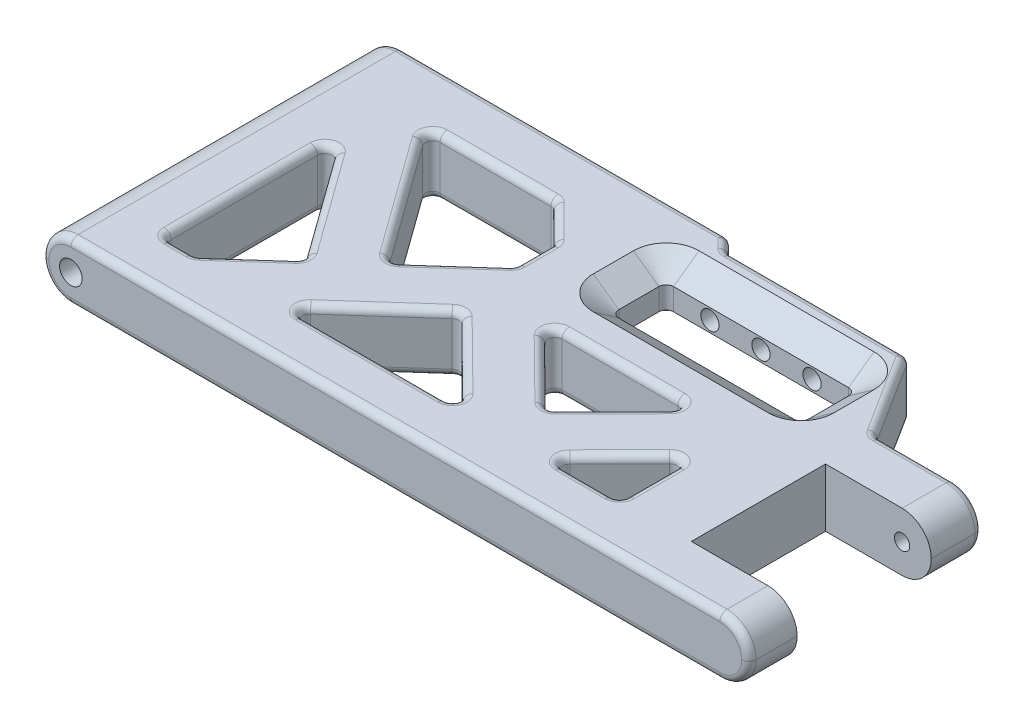
SolidWorks part; units mm, degrees
ref_plane "Plan de face" through (0, 0, 0) normal (0, 0, 1) x (1, 0, 0)
ref_plane "Plan de dessus" through (0, 0, 0) normal (0, 1, 0) x (1, 0, 0)
ref_plane "Plan de droite" through (0, 0, 0) normal (1, 0, 0) x (0, 0, -1)
sketch "Esquisse1" plane through (0, 0, 0) normal (0, 1, 0) x (1, 0, 0)
  line L0 (97, 2.25) -> (97, 9.25)
  line L19 (0, 22.75) -> (48.2586, 22.75)
  line L20 (0, 22.75) -> (0, -22.75)
  line L21 (32.0858, 15) -> (16.8865, 15)
  line L22 (16.0755, 13.415) -> (27.68, -2.6721)
  line L23 (37.2071, 10.2929) -> (32.7929, 14.7071)
  line L24 (37.5, 5.0644) -> (37.5, 9.5858)
  line L25 (29.1571, -2.833) -> (37.166, 4.3185)
  line L26 (21.8025, -8.1987) -> (11.811, 5.6522)
  line L27 (10, 5.0672) -> (10, -15)
  line L28 (14.6959, -15.7459) -> (21.6575, -9.5296)
  line L29 (38.632, -5.0977) -> (28.3777, -14.2541)
  line L30 (49.2684, -14.2886) -> (40.0009, -5.1322)
  line L31 (47.9211, -1.7114) -> (55.9463, -9.6404)
  line L32 (11, -16) -> (14.0298, -16)
  line L33 (29.0437, -16) -> (48.5656, -16)
  line L35 (97, -22.75) -> (0, -22.75)
  line L64 (48.9737, 22.449) -> (50.1934, 21.201)
  line L65 (50.9086, 20.9) -> (74.5358, 20.9)
  line L67 (48.5, 15.4) -> (72.5, 15.4)
  line L69 (47.5, 8.9) -> (47.5, 14.4)
  line L72 (72.5, 7.9) -> (48.5, 7.9)
  line L75 (73.5, 14.4) -> (73.5, 8.9)
  line L78 (75.3812, 20.4342) -> (82.1547, 9.7158)
  line L79 (83, 9.25) -> (97, 9.25)
  line L80 (97, -22.75) -> (97, -16.15)
  line L82 (82.5, 2.25) -> (82.5, -16.15)
  line L83 (97, 2.25) -> (82.5, 2.25)
  line L86 (82.5, -16.15) -> (97, -16.15)
  line L87 (64.4832, 0) -> (48.6239, 0)
  line L88 (57.3605, -9.6319) -> (65.1945, -1.7028)
  line L89 (64.7086, -16) -> (71.5, -16)
  line L90 (72.5, -15) -> (72.5, -8.1262)
  line L91 (70.7886, -7.4234) -> (63.9973, -14.2972)
  arc A16 (16.8865, 15) -> (16.0755, 13.415) centre (16.8865, 14) ccw
  arc A17 (32.7929, 14.7071) -> (32.0858, 15) centre (32.0858, 14) ccw
  arc A18 (37.5, 9.5858) -> (37.2071, 10.2929) centre (36.5, 9.5858) ccw
  arc A19 (37.166, 4.3185) -> (37.5, 5.0644) centre (36.5, 5.0644) ccw
  arc A20 (27.68, -2.6721) -> (29.1571, -2.833) centre (28.491, -2.0871) ccw
  arc A21 (21.6575, -9.5296) -> (21.8025, -8.1987) centre (20.9914, -8.7837) ccw
  arc A22 (11.811, 5.6522) -> (10, 5.0672) centre (11, 5.0672) ccw
  arc A23 (40.0009, -5.1322) -> (38.632, -5.0977) centre (39.298, -5.8436) ccw
  arc A24 (48.6239, 0) -> (47.9211, -1.7114) centre (48.6239, -1) ccw
  arc A25 (10, -15) -> (11, -16) centre (11, -15) ccw
  arc A26 (14.0298, -16) -> (14.6959, -15.7459) centre (14.0298, -15) ccw
  arc A27 (28.3777, -14.2541) -> (29.0437, -16) centre (29.0437, -15) ccw
  arc A28 (48.5656, -16) -> (49.2684, -14.2886) centre (48.5656, -15) ccw
  arc A45 (48.9737, 22.449) -> (48.2586, 22.75) centre (48.2586, 21.75) ccw
  arc A46 (50.1934, 21.201) -> (50.9086, 20.9) centre (50.9086, 21.9) ccw
  arc A47 (48.5, 15.4) -> (47.5, 14.4) centre (48.5, 14.4) ccw
  arc A48 (47.5, 8.9) -> (48.5, 7.9) centre (48.5, 8.9) ccw
  arc A49 (73.5, 14.4) -> (72.5, 15.4) centre (72.5, 14.4) ccw
  arc A50 (72.5, 7.9) -> (73.5, 8.9) centre (72.5, 8.9) ccw
  arc A51 (75.3812, 20.4342) -> (74.5358, 20.9) centre (74.5358, 19.9) ccw
  arc A52 (82.1547, 9.7158) -> (83, 9.25) centre (83, 10.25) ccw
  arc A55 (65.1945, -1.7028) -> (64.4832, 0) centre (64.4832, -1) ccw
  arc A56 (55.9463, -9.6404) -> (57.3605, -9.6319) centre (56.6492, -8.9291) ccw
  arc A57 (63.9973, -14.2972) -> (64.7086, -16) centre (64.7086, -15) ccw
  arc A58 (71.5, -16) -> (72.5, -15) centre (71.5, -15) ccw
  arc A59 (72.5, -8.1262) -> (70.7886, -7.4234) centre (71.5, -8.1262) ccw
  dimension "D4" = 1
  dimension "D1" = 97
  dimension "D2" = 45.5
  dimension "D3" = 32
  dimension "D5" = 26
  dimension "D6" = 7.5
  dimension "D7" = 5.5
  dimension "D8" = 23.5
  dimension "D9" = 43.65
  dimension "D10" = 7
  dimension "D11" = 6.6
  dimension "D12" = 14.5
  dimension "D13" = 2.65
  dimension "D14" = 8.4642
  dimension "D15" = 14
  dimension "D16" = 23.6273
  dimension "D17" = 8
  dimension "D18" = 8
  dimension "D19" = 8
  dimension "D20" = 8
  dimension "D21" = 10
extrude "Boss.-Extru.1" add sketch "Esquisse1" along normal blind 4 and the other way blind 4
fillet "Congé1" radius 4 6 edges at (0, 4, 0) (97, -4, -5.75) (97, -4, 19.45) (97, 4, 19.45) (97, 4, -5.75) (0, -4, 0)
fillet "Congé2" radius 1 100 edges at (71.8799, -4, 7.2012) (72.5, -4, 11.5631) (72.2071, -4, 15.7071) (68.1043, -4, 16) (63.7859, -4, 15.3855) (47.6989, -4, 0.6201) (56.5535, -4, 0) (65.4059, -4, 0.6145) (61.2775, -4, 5.6674) (56.6552, -4, 9.929) (37.4127, -4, -4.6558) (33.1616, -4, -0.7428) (28.3828, -4, 3.0812) (21.8778, -4, -5.3714) (15.9963, -4, -14.4555) (24.4861, -4, -15) (32.4685, -4, -14.9239) (35, -4, -12.5) (37.4239, -4, -9.9685) (39.3233, -4, 4.8439) (44.6346, -4, 9.7104) (49.4906, -4, 15.3799) (38.8047, -4, 16) (28.1094, -4, 15.3564) (14.3863, -4, 15.9343) (12.5149, -4, 16) (10.2929, -4, 15.7071) (10, -4, 4.9664) (10.6926, -4, -6.0187) (16.8067, -4, 1.2733) (21.9856, -4, 8.892) (49.4906, 4, 15.3799) (38.8047, 4, 16) (28.1094, 4, 15.3564) (33.5048, 4, 9.6759) (39.3233, 4, 4.8439) (71.8799, 4, 7.2012) (72.5, 4, 11.5631) (72.2071, 4, 15.7071) (68.1043, 4, 16) (63.7859, 4, 15.3855) (65.4059, 4, 0.6145) (61.2775, 4, 5.6674) (56.6552, 4, 9.929) (51.9337, 4, 5.6759) (47.6989, 4, 0.6201) (15.9963, 4, -14.4555) (24.4861, 4, -15) (32.4685, 4, -14.9239) (35, 4, -12.5) (37.4239, 4, -9.9685) (37.5, 4, -7.3251) (37.4127, 4, -4.6558) (33.1616, 4, -0.7428) (28.3828, 4, 3.0812) (10.6926, 4, -6.0187) (16.8067, 4, 1.2733) (21.9856, 4, 8.892) (18.1767, 4, 12.6378) (14.3863, 4, 15.9343) (12.5149, 4, 16) (10.2929, 4, 15.7071) (48.5, 4, 22.75) (95.8284, 2.8284, 22.75) (95.8284, -2.8284, 22.75) (48.5, -4, 22.75) (1.1716, -2.8284, 22.75) (1.1716, -2.8284, -22.75) (26.1293, -4, -22.75) (48.6465, -4, -22.6717) (49.5836, -4, -21.825) (50.5206, -4, -20.9783) (62.7222, -4, -20.9) (75.0184, -4, -20.7758) (78.7679, -4, -15.075) (82.5174, -4, -9.3742) (88, -4, -9.25) (95.8284, -2.8284, -9.25) (95.8284, 2.8284, -9.25) (88, 4, -9.25) (82.5174, 4, -9.3742) (78.7679, 4, -15.075) (75.0184, 4, -20.7758) (62.7222, 4, -20.9) (50.5206, 4, -20.9783) (49.5836, 4, -21.825) (48.6465, 4, -22.6717) (26.1293, 4, -22.75) (67.393, -4, 10.8603) (51.9337, -4, 5.6759) (37.5, -4, -7.3251) (33.5048, -4, 9.6759) (18.1767, -4, 12.6378) (44.6346, 4, 9.7104) (67.393, 4, 10.8603) (56.5535, 4, 0) (21.8778, 4, -5.3714) (10, 4, 4.9664) (1.1716, 2.8284, 22.75) (1.1716, 2.8284, -22.75)
chamfer "Chanfrein2" distance 3.5 distance2 2.5 8 edges at (60.5, 4, -7.9) (73.2071, 4, -8.1929) (47.7929, 4, -8.1929) (73.5, 4, -11.65) (47.5, 4, -11.65) (73.2071, 4, -15.1071) (47.7929, 4, -15.1071) (60.5, 4, -15.4) first distance on face at (38.9867, 4, 11.7077)
chamfer "Chanfrein3" distance 2.5 distance2 3.5 8 edges at (60.5, -4, -7.9) (73.2071, -4, -8.1929) (47.7929, -4, -8.1929) (73.5, -4, -11.65) (47.5, -4, -11.65) (73.2071, -4, -15.1071) (47.7929, -4, -15.1071) (60.5, -4, -15.4) first distance on face at (60.5, -1.25, -7.9) first distance on face at (73.1036, -1.25, -8.2964) first distance on face at (47.8964, -1.25, -8.2964) first distance on face at (73.5, -1.25, -11.65) first distance on face at (47.5, -1.25, -11.65) first distance on face at (73.1036, -1.25, -15.0036) first distance on face at (47.8964, -1.25, -15.0036) first distance on face at (60.5, -1.25, -15.4)
sketch "Esquisse6" plane through (0, 0, 0) normal (0, 0, 1) x (1, 0, 0)
  circle A1 centre (93, 0) radius 1.05
  dimension "D1" = 2.1
extrude "Enlèv. mat.-Extru.1" cut sketch "Esquisse6" against normal through all and the other way offset from surface 1 other way up to face at (48.5, 0, 22.75)
sketch "Esquisse10" plane through (0, 0, 0) normal (0, 0, 1) x (1, 0, 0)
  circle A0 centre (4, 0) radius 1.55
  dimension "D1" = 3.1
extrude "Enlèv. mat.-Extru.2" cut sketch "Esquisse10" against normal through all and the other way through all
hole_wizard "Trou taraudé M31" positions "Esquisse8" profile "Esquisse7" tap size "M3" standard "ISO"
sketch "Esquisse8" plane through (0, 0, -20.9) normal (0, 0, -1) x (-1, 0, 0)
  line L0 (-72.5, 1.5) -> (-48.5, 1.5) construction
  point P0 (-60.5, 0)
  point P2 (-53.5, 0)
  point P4 (-67.5, 0)
  point P8 (-60.5, 1.5)
  dimension "D1" = 7
  dimension "D2" = 7
sketch "Esquisse7" plane through (60.5, 0, -20.9) normal (1, 0, 0) x (0, 1, 0)
  line L0 (0, 0) -> (0, 16.7511)
  line L1 (0, 16.7511) -> (1.25, 16)
  line L2 (1.25, 16) -> (1.25, 0)
  line L5 (1.25, 0) -> (0, 0)
  line L10 (0, 16.7511) -> (-1.25, 16) construction
  line L11 (0, -6.35) -> (0, 107.95) construction
  dimension "Diamètre du trou pour taraudage" = 2.5
  dimension "Profondeur du trou pour taraudage" = 16
  dimension "Angle de pointe" = 118
cosmetic thread "Filetage de perçage1" parameters "D1"=16, "D2"=3
cosmetic thread "Filetage de perçage2" parameters "D1"=16, "D2"=3
cosmetic thread "Filetage de perçage3" parameters "D1"=16, "D2"=3
hole_wizard "Trou pour taraudage pour trou taraudé M31" positions "Esquisse13" profile "Esquisse14" hole size "M3" standard "ISO"
sketch "Esquisse13" plane through (0, 0, -9.25) normal (0, 0, -1) x (-1, 0, 0)
  point P0 (-93, 0)
sketch "Esquisse14" plane through (93, 0, -9.25) normal (1, 0, 0) x (0, 1, 0)
  line L0 (0, 0) -> (0, 3.8112)
  line L1 (0, 3.8112) -> (1.35, 3)
  line L2 (1.35, 3) -> (1.35, 0)
  line L5 (1.35, 0) -> (0, 0)
  line L10 (0, 3.8112) -> (-1.35, 3) construction
  line L11 (0, -6.35) -> (0, 107.95) construction
  dimension "Diamètre du perçage" = 2.7
  dimension "Profondeur du perçage" = 3
  dimension "Angle de pointe" = 118
